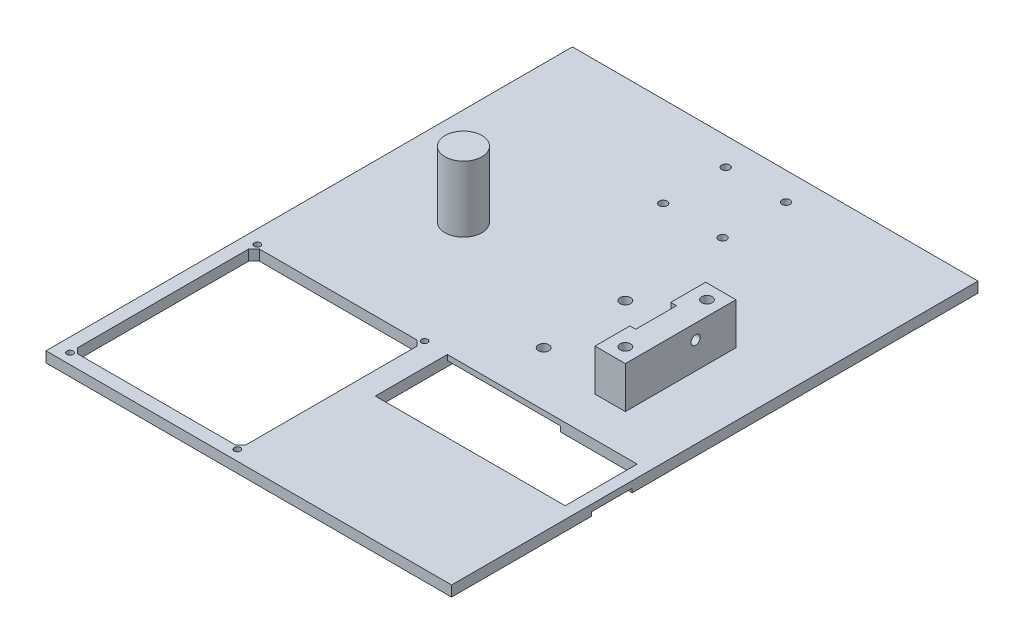
SolidWorks part; units mm, degrees
ref_plane "Front Plane" through (0, 0, 0) normal (0, 0, 1) x (1, 0, 0)
ref_plane "Top Plane" through (0, 0, 0) normal (0, 1, 0) x (1, 0, 0)
ref_plane "Right Plane" through (0, 0, 0) normal (1, 0, 0) x (0, 0, -1)
sketch "Sketch1" plane through (0, 0, 0) normal (0, 1, 0) x (1, 0, 0)
  line L0 (-36.95, 39.49) -> (36.95, 39.49)
  line L1 (-31.95, -34.49) -> (31.95, -34.49)
  line L2 (-31.95, -34.49) -> (-31.95, 34.49)
  line L3 (-31.95, 34.49) -> (31.95, 34.49)
  line L4 (31.95, -34.49) -> (31.95, 34.49)
  line L5 (-31.95, -34.49) -> (31.95, 34.49) construction
  line L6 (-31.95, 34.49) -> (31.95, -34.49) construction
  line L7 (36.95, -39.49) -> (36.95, 39.49)
  line L8 (-36.95, -39.49) -> (36.95, -39.49)
  line L9 (-36.95, -39.49) -> (-36.95, 39.49)
  point P0 (0, 0)
  dimension "D1" = 63.9
  dimension "D2" = 68.98
  dimension "D3" = 5
extrude "Boss-Extrude1" add sketch "Sketch1" along normal blind 4
sketch "Sketch2" plane through (0, 4, 0) normal (0, 1, 0) x (1, 0, 0)
  line L0 (-31.95, -34.49) -> (31.95, -34.49) construction
  line L1 (31.95, -34.49) -> (31.95, 34.49) construction
  line L2 (31.95, 34.49) -> (-31.95, 34.49) construction
  line L3 (-31.95, 34.49) -> (-31.95, -34.49) construction
  line L4 (-36.95, 39.49) -> (-36.95, -39.49)
  line L5 (-36.95, -39.49) -> (36.95, -39.49)
  line L6 (36.95, -39.49) -> (36.95, 39.49)
  line L7 (36.95, 39.49) -> (-36.95, 39.49)
  line L8 (-36.95, 39.49) -> (-36.95, -39.49)
  line L9 (-36.95, -39.49) -> (36.95, -39.49)
  line L10 (36.95, -39.49) -> (36.95, 39.49)
  line L11 (36.95, 39.49) -> (-36.95, 39.49)
  line L12 (-31.95, -34.49) -> (31.95, -34.49)
  line L13 (31.95, -34.49) -> (31.95, 34.49)
  line L14 (31.95, 34.49) -> (-31.95, 34.49)
  line L15 (-31.95, 34.49) -> (-31.95, -34.49)
  line L16 (-31.95, 34.49) -> (31.95, -34.49)
  line L17 (31.95, 34.49) -> (-31.95, -34.49)
  line L19 (-31.75, -35.56) -> (31.75, -35.56)
  line L20 (-31.75, -35.56) -> (-31.75, 35.56)
  line L21 (-31.75, 35.56) -> (31.75, 35.56)
  line L22 (31.75, -35.56) -> (31.75, 35.56)
  line L23 (-31.75, -35.56) -> (31.75, 35.56) construction
  line L24 (-31.75, 35.56) -> (31.75, -35.56) construction
  circle A0 centre (-31.75, 35.56) radius 1.1811
  circle A1 centre (31.75, 35.56) radius 1.1811
  circle A2 centre (-31.75, -35.56) radius 1.1811
  circle A3 centre (31.75, -35.56) radius 1.1811
  point P6 (0, 0)
  dimension "D4" = 2.3622
  dimension "D5" = 2.3622
  dimension "D6" = 2.3622
  dimension "D7" = 2.3622
  dimension "D2" = 63.5
  dimension "D3" = 71.12
  dimension "D1" = 0
extrude "Cut-Extrude1" cut sketch "Sketch2" against normal through all contours A0 | A1 | A3 | A2
sketch "Sketch4" plane through (0, 4, 0) normal (0, 1, 0) x (1, 0, 0)
  line L0 (-31.95, 34.396) -> (-31.95, -34.396) construction
  line L1 (31.2499, 34.49) -> (-31.2499, 34.49) construction
  line L2 (-31.95, 34.396) -> (-31.95, -34.396)
  line L3 (31.2499, 34.49) -> (-31.2499, 34.49)
  line L4 (-36.95, 39.49) -> (-36.95, -39.49)
  line L5 (-36.95, -39.49) -> (36.95, -39.49)
  line L6 (36.95, -39.49) -> (36.95, 39.49)
  line L7 (36.95, 39.49) -> (-36.95, 39.49)
  line L8 (-36.95, 39.49) -> (-36.95, -39.49)
  line L9 (-36.95, -39.49) -> (36.95, -39.49)
  line L10 (36.95, -39.49) -> (36.95, 39.49)
  line L11 (36.95, 39.49) -> (-36.95, 39.49)
  line L12 (-31.2499, 34.49) -> (-36.95, 34.49)
  line L13 (-31.95, 34.396) -> (-31.95, 39.49)
  line L14 (-31.95, 34.49) -> (-29.95, 34.49)
  line L15 (-31.95, 34.49) -> (-31.95, 32.49)
  line L16 (-31.95, 32.49) -> (-29.95, 34.49)
  arc A0 (-31.2499, 34.49) -> (-31.95, 34.396) centre (-31.75, 35.56) ccw construction
  arc A1 (-31.2499, 34.49) -> (-31.95, 34.396) centre (-31.75, 35.56) ccw
  circle A2 centre (-31.75, 35.56) radius 1.1811
  point P8 (-31.95, 34.49)
  line M11 (-31.2499, 34.49) -> (31.2499, 34.49)
  dimension "D2" = 2
  dimension "D3" = 2
  dimension "D1" = 0
extrude "Boss-Extrude3" add sketch "Sketch4" along direction (0, -1, 0) on the side against the normal up to surface (4 mm away) contours A2 L2 L16 M11 region at (-31.2719, 4, -33.8047) up to face at (0, 0, 0)
ref_plane "Plane1" through (0, 0, 0) normal (0, 0, -1) x (-1, 0, 0)
mirror "Mirror1" about plane through (0, 0, 0) normal (0, 0, -1) of "Boss-Extrude3"
ref_plane "Plane2" through (0, 0, 0) normal (-1, 0, 0) x (0, 0, 1)
mirror "Mirror2" about plane through (0, 0, 0) normal (-1, 0, 0) of "Mirror1", "Boss-Extrude3"
sketch "Sketch5" plane through (0, 4, 0) normal (0, 1, 0) x (1, 0, 0)
  line L0 (36.95, -39.49) -> (36.95, 39.49) construction
  line L1 (40.45, 8.14) -> (112.55, 8.14)
  line L2 (40.45, 8.14) -> (40.45, 35.49)
  line L3 (40.45, 35.49) -> (112.55, 35.49)
  line L4 (112.55, 8.14) -> (112.55, 35.49)
  line L5 (40.45, 8.14) -> (112.55, 35.49) construction
  line L6 (40.45, 35.49) -> (112.55, 8.14) construction
  line L7 (36.95, -39.49) -> (36.95, 39.49)
  line L8 (-36.95, -39.49) -> (36.95, -39.49) construction
  line L9 (-36.95, -39.49) -> (36.95, -39.49)
  line L10 (36.95, -39.49) -> (36.95, -34.3454)
  line L12 (36.95, -39.49) -> (117.05, -39.49)
  line L13 (36.95, -39.49) -> (36.95, 39.49)
  line L14 (36.95, 39.49) -> (117.05, 39.49)
  line L15 (117.05, -39.49) -> (117.05, 39.49)
  point P0 (76.5, 21.815)
  point P5 (0, 0)
  point P11 (36.95, -34.3454)
  point P13 (42.0242, 35.4834)
  line M22 (36.95, -39.49) -> (36.95, 39.49)
  dimension "D1" = 72.1
  dimension "D2" = 27.35
  dimension "D3" = 3.5
  dimension "D4" = 4
  dimension "D5" = 4.5
extrude "Boss-Extrude4" add sketch "Sketch5" against normal up to surface (4 mm away) contours L12 L15 L14 L7 L4 L1 L2 L3 M22 region at (77.2264, 4, 9.8792) up to face at (0, 0, 0)
sketch "Sketch6" plane through (0, 4, 0) normal (0, 1, 0) x (1, 0, 0)
  line L1 (-36.95, 39.49) -> (117.05, 39.49)
  line L2 (-36.95, 39.49) -> (-36.95, 160.381)
  line L3 (-36.95, 160.381) -> (117.05, 160.381)
  line L4 (-36.95, 39.49) -> (-36.95, -39.49)
  line L5 (-36.95, -39.49) -> (117.05, -39.49)
  line L6 (117.05, -39.49) -> (117.05, 39.49)
  line L7 (117.05, 39.49) -> (-36.95, 39.49)
  line L8 (-36.95, 39.49) -> (-36.95, -39.49)
  line L9 (-36.95, -39.49) -> (117.05, -39.49)
  line L10 (117.05, -39.49) -> (117.05, 39.49)
  line L11 (117.05, 39.49) -> (-36.95, 39.49)
  line L12 (117.05, 39.49) -> (117.05, 160.381)
  line M19 (117.05, 39.49) -> (-36.95, 39.49)
  dimension "D1" = 0
extrude "Boss-Extrude5" add sketch "Sketch6" along direction (0, -1, 0) on the side against the normal up to surface (4 mm away) separate body contours L12 L3 L2 M19 region at (40.05, 4, -99.9355) up to face at (0, 0, 0)
combine bodies "Combine1" operation type add bodies to combine 108 107
sketch "Sketch7" plane through (0, 4, 0) normal (0, 1, 0) x (1, 0, 0)
  line L0 (93.0315, 92.49) -> (51.0315, 50.49) construction
  line L1 (51.0315, 50.49) -> (93.0315, 50.49) construction
  line L2 (51.0315, 50.49) -> (51.0315, 92.49) construction
  line L3 (51.0315, 92.49) -> (93.0315, 92.49) construction
  line L4 (93.0315, 50.49) -> (93.0315, 92.49) construction
  line L5 (40.45, 35.49) -> (112.55, 35.49) construction
  line L7 (56.5315, 55.99) -> (87.5315, 55.99)
  line L8 (56.5315, 55.99) -> (56.5315, 86.99)
  line L9 (56.5315, 86.99) -> (87.5315, 86.99)
  line L10 (87.5315, 55.99) -> (87.5315, 86.99)
  line L11 (56.5315, 55.99) -> (87.5315, 86.99) construction
  line L12 (56.5315, 86.99) -> (87.5315, 55.99) construction
  circle A0 centre (72.0315, 71.49) radius 3.618 construction
  circle A1 centre (56.5315, 86.99) radius 2
  circle A2 centre (87.5315, 86.99) radius 2
  circle A3 centre (87.5315, 55.99) radius 2
  circle A4 centre (56.5315, 55.99) radius 2
  dimension "D6" = 4
  dimension "D7" = 4
  dimension "D8" = 4
  dimension "D9" = 4
  dimension "D1" = 42
  dimension "D2" = 42
  dimension "D3" = 15
  dimension "D4" = 31
  dimension "D5" = 31
sketch "Sketch8" plane through (0, 4, 0) normal (0, 1, 0) x (1, 0, 0)
  line L0 (66.4509, 168.99) -> (66.4509, 162.95) construction
  line L1 (30.4509, 168.99) -> (66.4509, 168.99) construction
  line L2 (30.4509, 168.99) -> (30.4509, 128.49) construction
  line L3 (30.4509, 128.49) -> (66.4509, 128.49) construction
  line L4 (66.4509, 168.99) -> (66.4509, 128.49) construction
  line L5 (30.4509, 128.49) -> (56.7509, 128.49) construction
  line L6 (30.4509, 128.49) -> (30.4509, 168.99) construction
  line L7 (30.4509, 168.99) -> (56.7509, 168.99) construction
  line L8 (56.7509, 128.49) -> (56.7509, 168.99) construction
  line L9 (56.7509, 168.99) -> (59.3009, 168.99) construction
  line L10 (56.7509, 168.99) -> (56.7509, 176.49) construction
  line L11 (56.7509, 176.49) -> (59.3009, 176.49) construction
  line L12 (59.3009, 168.99) -> (59.3009, 176.49) construction
  line L13 (56.7509, 128.49) -> (59.3009, 128.49) construction
  line L14 (56.7509, 128.49) -> (56.7509, 120.99) construction
  line L15 (56.7509, 120.99) -> (59.3009, 120.99) construction
  line L16 (59.3009, 128.49) -> (59.3009, 120.99) construction
  line L17 (66.4509, 128.49) -> (66.4509, 155.09) construction
  line L18 (72.4509, 154.0488) -> (72.4509, 163.9912) construction
  line L19 (66.4509, 162.95) -> (72.4509, 162.95) construction
  line L20 (66.4509, 162.95) -> (66.4509, 155.09) construction
  line L21 (66.4509, 155.09) -> (72.4509, 155.09) construction
  line L22 (72.4509, 162.95) -> (72.4509, 155.09) construction
  line L23 (51.0315, 92.49) -> (93.0315, 92.49) construction
  line L24 (72.4509, 163.9912) -> (74.4509, 163.9912) construction
  line L25 (72.4509, 163.9912) -> (72.4509, 154.0488) construction
  line L26 (72.4509, 154.0488) -> (74.4509, 154.0488) construction
  line L27 (74.4509, 163.9912) -> (74.4509, 154.0488) construction
  point P19 (72.4509, 159.02)
  point P21 (5.1828, 105.0808)
  point P22 (-8.785, 150.0873)
  point P23 (56.7509, 111.9821)
  dimension "D1" = 40.5
  dimension "D2" = 36
  dimension "D3" = 26.3
  dimension "D4" = 2.55
  dimension "D5" = 2.55
  dimension "D6" = 7.5
  dimension "D7" = 7.5
  dimension "D8" = 6.04
  dimension "D9" = 26.6
  dimension "D10" = 6
  dimension "D11" = 2
  dimension "D12" = 36
sketch "Sketch10" plane through (0, 4, 0) normal (0, 1, 0) x (1, 0, 0)
  line L0 (51.0315, 92.49) -> (93.0315, 92.49) construction
  line L1 (25.0315, 147.99) -> (61.0315, 147.99)
  line L2 (25.0315, 147.99) -> (25.0315, 127.99)
  line L3 (25.0315, 127.99) -> (61.0315, 127.99)
  line L4 (61.0315, 147.99) -> (61.0315, 127.99)
  line L5 (51.0315, 92.49) -> (93.0315, 92.49)
  line L6 (51.0315, 92.49) -> (61.0315, 92.49)
  line L7 (61.0315, 92.49) -> (61.0315, 151.0418) construction
  line L8 (31.7451, 126.1304) -> (54.3309, 126.1304)
  line L9 (31.7451, 149.8943) -> (54.6365, 149.8943)
  line L10 (31.7451, 126.1304) -> (31.7451, 149.8943)
  circle A0 centre (31.7451, 126.1304) radius 1.5253
  circle A1 centre (54.3309, 126.1304) radius 1.5253
  circle A2 centre (31.7451, 149.8943) radius 1.5253
  circle A3 centre (54.6365, 149.8943) radius 1.5253
  point P16 (31.7451, 150.2868)
  dimension "D5" = 3.0506
  dimension "D6" = 3.0506
  dimension "D7" = 3.0506
  dimension "D8" = 3.0506
  dimension "D1" = 20
  dimension "D2" = 36
  dimension "D3" = 35.5
  dimension "D4" = 10
extrude "Cut-Extrude2" cut sketch "Sketch10" against normal through all contours A3 | A2 | A0 | A1
sketch "Sketch11" plane through (0, 4, 0) normal (0, 1, 0) x (1, 0, 0)
  line L0 (51.0315, 50.49) -> (93.0315, 50.49) construction
  line L1 (93.0315, 50.49) -> (93.0315, 92.49) construction
  line L2 (51.0315, 92.49) -> (93.0315, 92.49) construction
  line L3 (51.0315, 50.49) -> (51.0315, 92.49) construction
  line L4 (51.0315, 50.49) -> (93.0315, 50.49)
  line L5 (93.0315, 50.49) -> (93.0315, 92.49)
  line L6 (51.0315, 92.49) -> (93.0315, 92.49)
  line L7 (51.0315, 50.49) -> (51.0315, 92.49)
  circle A0 centre (72.0315, 71.49) radius 3.618 construction
  circle A1 centre (72.0315, 71.49) radius 3.618
  circle A2 centre (72.0315, 71.49) radius 3
  dimension "D1" = 6
extrude "Cut-Extrude3" cut sketch "Sketch11" against normal through all contours A2 region at (72.0315, 4, -71.49)
extrude "Cut-Extrude4" cut sketch "Sketch7" against normal through all contours A1 | A2 | A3 | A4
sketch "Sketch12" plane through (0, 4, 0) normal (0, 1, 0) x (1, 0, 0)
  line L0 (93.0315, 50.49) -> (93.0315, 92.49) construction
  line L1 (93.0315, 50.49) -> (93.0315, 92.49)
  line L2 (51.0315, 92.49) -> (93.0315, 92.49) construction
  line L3 (51.0315, 92.49) -> (93.0315, 92.49)
  line L4 (51.0315, 50.49) -> (93.0315, 50.49) construction
  line L5 (51.0315, 50.49) -> (93.0315, 50.49)
  line L7 (93.0315, 92.49) -> (81.5315, 92.49)
  line L8 (93.0315, 92.49) -> (93.0315, 50.49)
  line L9 (93.0315, 50.49) -> (81.5315, 50.49)
  line L10 (81.5315, 92.49) -> (81.5315, 50.49)
  circle M2 centre (87.5315, 86.99) radius 2
  circle M3 centre (87.5315, 55.99) radius 2
  dimension "D1" = 11.5
extrude "Boss-Extrude7" add sketch "Sketch12" along normal blind 15.8 contours L3 L10 L5 L1 M2 M3 region at (87.2678, 4, -71.49)
sketch "Sketch13" plane through (0, 19.8, 0) normal (0, 1, 0) x (1, 0, 0)
  line L0 (81.5315, 63.74) -> (81.5315, 79.24)
  line L2 (81.5315, 79.24) -> (83.7315, 79.24)
  line L3 (81.5315, 79.24) -> (81.5315, 63.74)
  line L4 (93.0315, 92.49) -> (81.5315, 92.49)
  line L5 (81.5315, 92.49) -> (81.5315, 50.49)
  line L6 (81.5315, 50.49) -> (93.0315, 50.49)
  line L7 (93.0315, 50.49) -> (93.0315, 92.49)
  line L8 (93.0315, 92.49) -> (81.5315, 92.49)
  line L9 (81.5315, 92.49) -> (81.5315, 50.49)
  line L10 (81.5315, 50.49) -> (93.0315, 50.49)
  line L11 (93.0315, 50.49) -> (93.0315, 92.49)
  line L12 (81.5315, 63.74) -> (83.7315, 63.74)
  line L13 (83.7315, 79.24) -> (83.7315, 63.74)
  point P7 (81.5315, 71.49)
  line M8 (81.5315, 92.49) -> (81.5315, 50.49)
  dimension "D2" = 15.5
  dimension "D3" = 2.2
  dimension "D1" = 0
extrude "Cut-Extrude5" cut sketch "Sketch13" against normal blind 2.2 contours L13 L2 L12 M8 region at (82.6315, 19.8, -71.49)
sketch "Sketch14" plane through (93.0315, 0, 0) normal (1, 0, 0) x (0, 0, -1)
  line L0 (92.49, 14.2) -> (77.19, 14.2)
  line L1 (92.49, 19.8) -> (92.49, 4) construction
  line L2 (77.19, 4) -> (77.19, 14.2)
  line L3 (50.49, 4) -> (92.49, 4) construction
  circle A0 centre (77.19, 14.2) radius 1.75
  dimension "D3" = 3.5
  dimension "D1" = 15.3
  dimension "D2" = 10.2
extrude "Cut-Extrude6" cut sketch "Sketch14" against normal through all contours A0
sketch "Sketch15" plane through (0, 4, 0) normal (0, 1, 0) x (1, 0, 0)
  circle A0 centre (0, 82.0665) radius 7
  dimension "D1" = 14
extrude "Boss-Extrude8" add sketch "Sketch15" along normal blind 25
sketch "Sketch16" plane through (0, 0, 0) normal (0, -1, 0) x (1, 0, 0)
  line L1 (40.45, -35.49) -> (83.45, -35.49)
  line L2 (40.45, -35.49) -> (40.45, -38.7598)
  line L3 (40.45, -38.7598) -> (83.45, -38.7598)
  line L4 (83.45, -35.49) -> (83.45, -38.7598)
  dimension "D1" = 43
extrude "Cut-Extrude7" cut sketch "Sketch16" against normal blind 2
sketch "Sketch17" plane through (0, 0, 0) normal (0, -1, 0) x (1, 0, 0)
  line L0 (112.55, -8.14) -> (112.55, -35.49) construction
  line L1 (112.55, -13.6081) -> (117.05, -13.6081)
  line L2 (112.55, -13.6081) -> (112.55, -29.0756)
  line L3 (112.55, -29.0756) -> (117.05, -29.0756)
  line L4 (117.05, -13.6081) -> (117.05, -29.0756)
  line L5 (117.05, 39.49) -> (117.05, -160.381) construction
extrude "Cut-Extrude8" cut sketch "Sketch17" against normal blind 1.5
